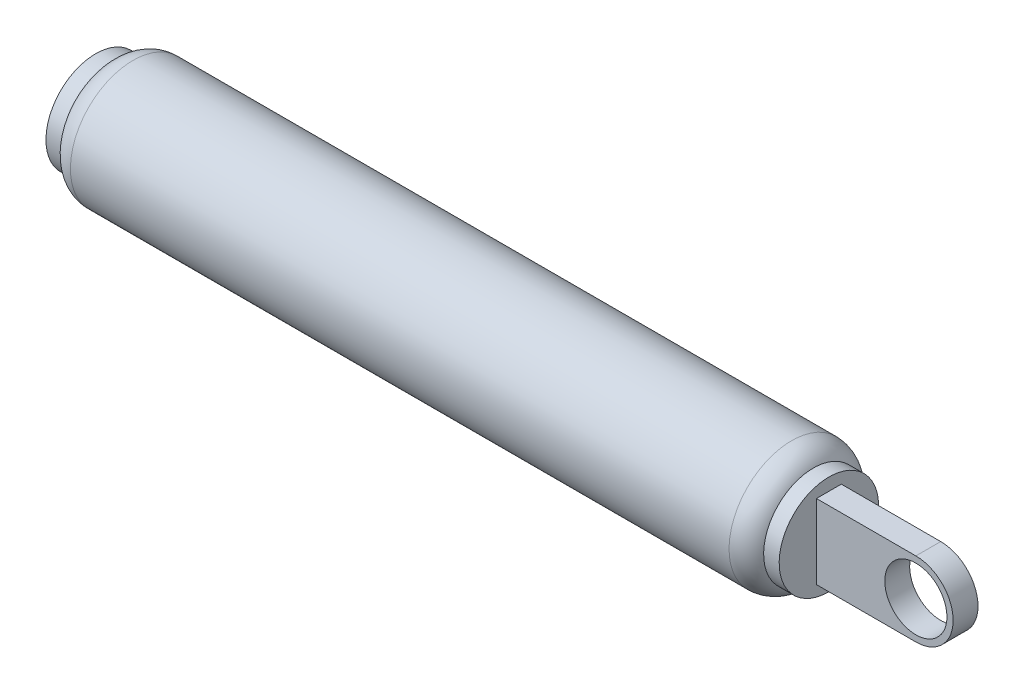
SolidWorks part; units mm, degrees
ref_plane "Front Plane" through (0, 0, 0) normal (0, 0, 1) x (1, 0, 0)
ref_plane "Top Plane" through (0, 0, 0) normal (0, 1, 0) x (1, 0, 0)
ref_plane "Right Plane" through (0, 0, 0) normal (1, 0, 0) x (0, 0, -1)
ref_plane "Plane1" through (0, 0, 0) normal (0, 0, -1) x (-1, 0, 0)
sketch "Sketch1" plane through (0, 0, 0) normal (0, 0, -1) x (-1, 0, 0)
  line L0 (-29.5, 4) -> (-29.5, 0)
  line L1 (-29.5, 0) -> (29.5, 0)
  line L2 (29.5, 0) -> (29.5, 4)
  line L3 (29.5, 4) -> (28.25, 4)
  line L4 (26.5, 5.0318) -> (-26.5, 5.0318)
  line L5 (-28.25, 4) -> (-29.5, 4)
  line L6 (-29.5, 0) -> (29.5, 0) construction
  arc A0 (28.25, 4) -> (26.5, 5.0318) centre (26.5, 3.0318) ccw
  arc A1 (-26.5, 5.0318) -> (-28.25, 4) centre (-26.5, 3.0318) ccw
  point P10 (0, 0)
  dimension "D5" = 2
  dimension "D1" = 4
  dimension "D2" = 53
  dimension "D3" = 1.25
  dimension "D4" = 59
revolve "Revolve1" add sketch "Sketch1" angle 360 about L6 reverse direction yes
ref_plane "Plane2" through (0, 0, 1) normal (0, 0, 1) x (1, 0, 0)
sketch "Sketch2" plane through (0, 0, 1) normal (0, 0, 1) x (1, 0, 0)
  line L0 (37.5, 3) -> (29.5, 3)
  line L1 (29.5, 3) -> (29.5, -3)
  line L2 (29.5, -3) -> (37.5, -3)
  line L5 (29.5, -4) -> (29.5, 4) construction
  arc A0 (37.5, -3) -> (37.5, 3) centre (37.5, 0) ccw
  point P8 (29.5, 0)
  dimension "D2" = 3
  dimension "D1" = 8
  dimension "D3" = 6
extrude "Boss-Extrude1" add sketch "Sketch2" against normal blind 2
hole_wizard "Ø6.0 (6) Diameter Hole1" positions "Sketch4" profile "Sketch3" hole size "Ø6.0" standard "ANSI Metric"
sketch "Sketch4" plane through (-29.5, 0, 0) normal (-1, 0, 0) x (0, 0, 1)
  point P0 (0, 0)
sketch "Sketch3" plane through (-29.5, 0, 0) normal (0, 1, 0) x (0, 0, 1)
  line L0 (0, 0) -> (0, 25)
  line L1 (0, 25) -> (3, 25)
  line L2 (3, 25) -> (3, 0)
  line L5 (3, 0) -> (0, 0)
  line L10 (0, 25) -> (-3, 25) construction
  line L11 (0, -6.35) -> (0, 107.95) construction
  dimension "Hole Dia." = 6
  dimension "Hole Depth" = 25
  dimension "Drill Angle" = 180
hole_wizard "Ø5.0 (5) Diameter Hole1" positions "Sketch6" profile "Sketch5" hole size "Ø5.0" standard "ANSI Metric"
sketch "Sketch6" plane through (0, 0, -1) normal (0, 0, -1) x (-1, 0, 0)
  arc A0 (-37.5, 3) -> (-37.5, -3) centre (-37.5, 0) ccw construction
  point P0 (-37.5, 0)
sketch "Sketch5" plane through (37.5, 0, -1) normal (1, 0, 0) x (0, 1, 0)
  line L0 (0, 0) -> (0, 6.0318)
  line L1 (0, 6.0318) -> (2.5, 6.0318)
  line L2 (2.5, 6.0318) -> (2.5, 0)
  line L5 (2.5, 0) -> (0, 0)
  line L11 (0, -6.35) -> (0, 107.95) construction
  dimension "Thru Hole Dia." = 5
  dimension "Thru Hole Depth" = 6.0318
ref_axis "Axis1" through (37.5, 0, 3.2933) along (0, 0, -1)
